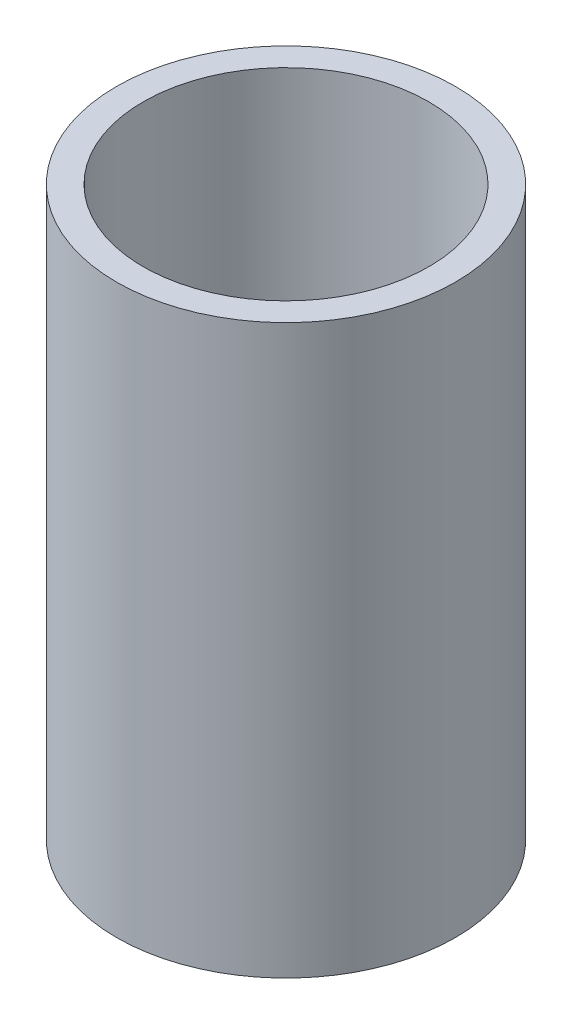
SolidWorks part; units mm, degrees
ref_plane "Front Plane" through (0, 0, 0) normal (0, 0, 1) x (1, 0, 0)
ref_plane "Top Plane" through (0, 0, 0) normal (0, 1, 0) x (1, 0, 0)
ref_plane "Right Plane" through (0, 0, 0) normal (1, 0, 0) x (0, 0, -1)
sketch "Sketch1" plane through (0, 0, 0) normal (0, 1, 0) x (1, 0, 0)
  circle A0 centre (0, 0) radius 25
  dimension "SLEEVE_OD" = 50
extrude "Boss-Extrude1" add sketch "Sketch1" along normal blind 83.7349
sketch "Sketch2" plane through (0, 0, 0) normal (0, 1, 0) x (1, 0, 0)
  circle A0 centre (0, 0) radius 21.0718
  dimension "BORE_D" = 42.1437
extrude "Cut-Extrude1" cut sketch "Sketch2" along normal through all
chamfer "Chamfer1" distance 3.108 angle 57.72 rebuild error yes
